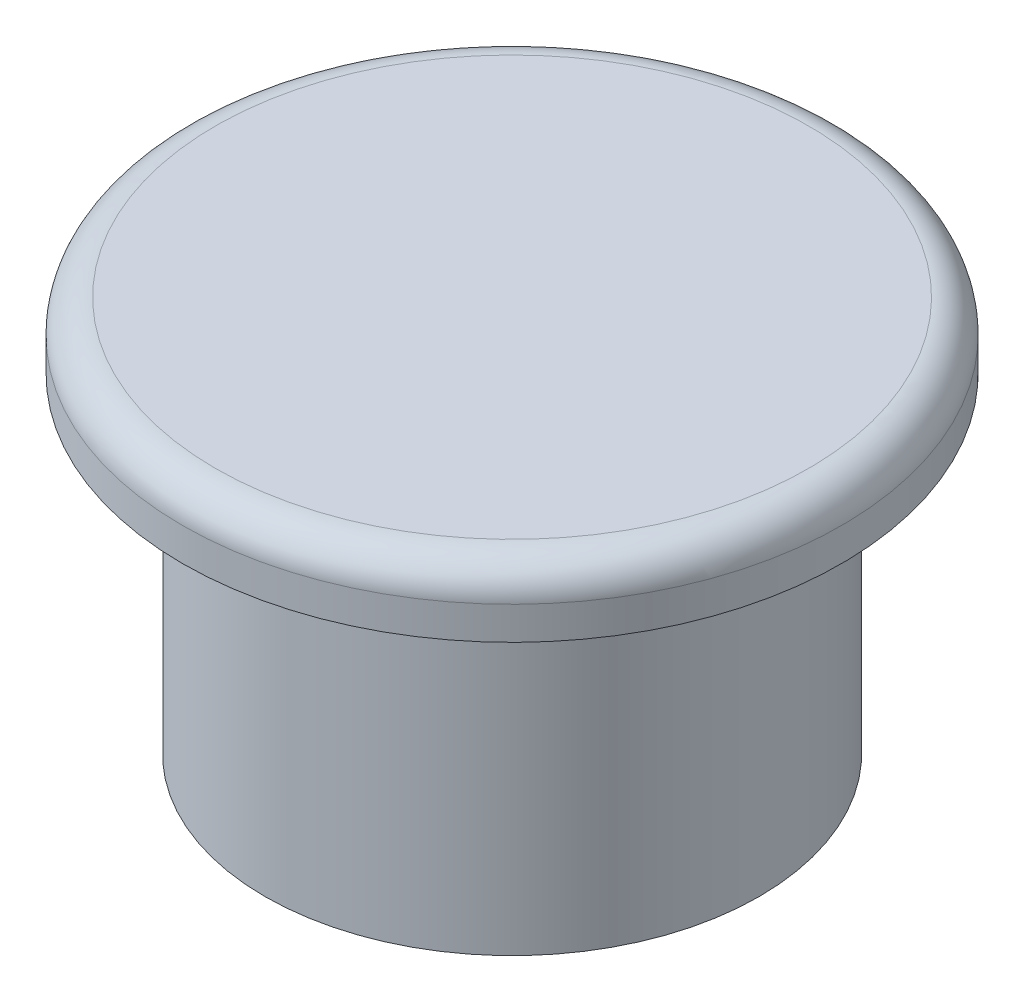
SolidWorks part; units mm, degrees
ref_plane "Front Plane" through (0, 0, 0) normal (0, 0, 1) x (1, 0, 0)
ref_plane "Top Plane" through (0, 0, 0) normal (0, 1, 0) x (1, 0, 0)
ref_plane "Right Plane" through (0, 0, 0) normal (1, 0, 0) x (0, 0, -1)
sketch "Sketch1" plane through (0, 0, 0) normal (0, 1, 0) x (1, 0, 0)
  circle A0 centre (0, 0) radius 0.625
  circle A1 centre (0, 0) radius 0.75
  dimension "D1" = 1.25
  dimension "D2" = 1.5
extrude "Boss-Extrude1" add sketch "Sketch1" along normal blind 1
sketch "Sketch2" plane through (0, 1, 0) normal (0, 1, 0) x (1, 0, 0)
  circle A0 centre (0, 0) radius 1
extrude "Boss-Extrude2" add sketch "Sketch2" along normal blind 0.2
fillet "Fillet1" radius 0.1 1 edges at (0, 1.2, 1)
